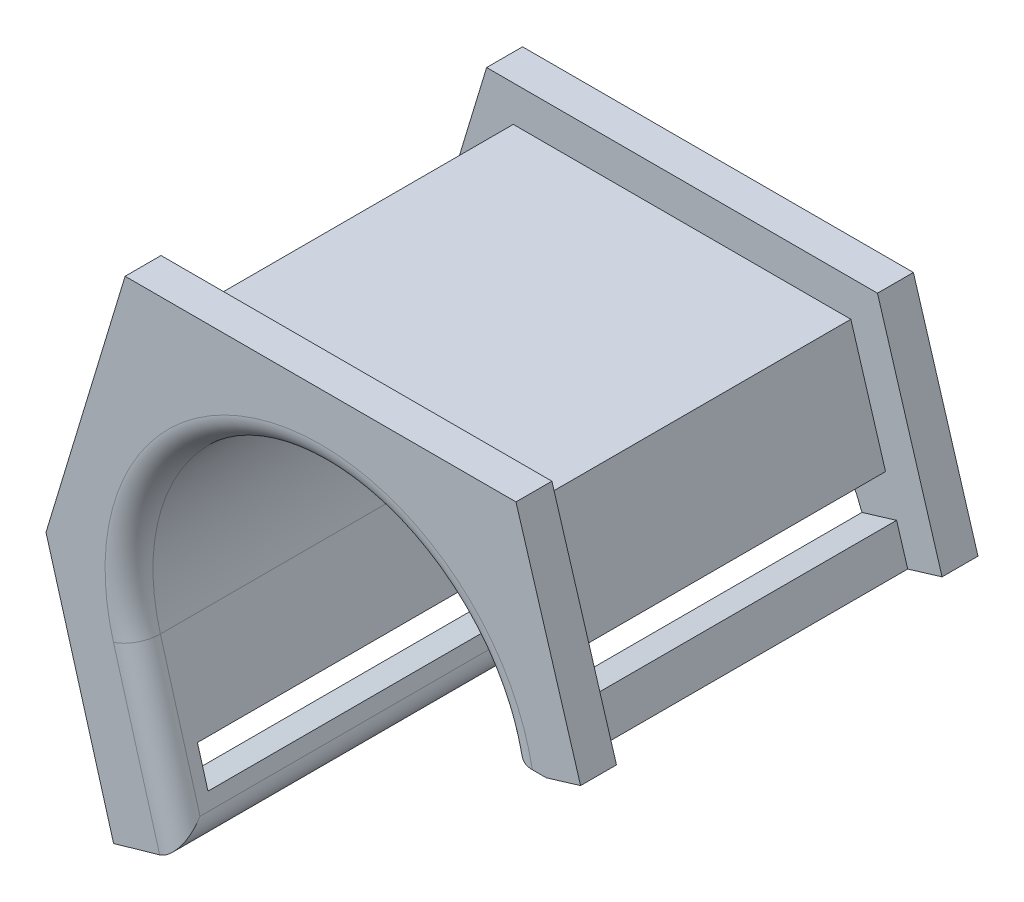
SolidWorks part; units mm, degrees
ref_plane "Front Plane" through (0, 0, 0) normal (0, 0, 1) x (1, 0, 0)
ref_plane "Top Plane" through (0, 0, 0) normal (0, 1, 0) x (1, 0, 0)
ref_plane "Right Plane" through (0, 0, 0) normal (1, 0, 0) x (0, 0, -1)
sketch "Sketch1" plane through (0, 0, 0) normal (0, 0, 1) x (1, 0, 0)
  line L3 (7.05, 9.5) -> (-7.05, 9.5)
  line L8 (9.4257, 1.6517) -> (7.05, 9.5)
  line L10 (-7.05, 9.5) -> (-9.9038, 0.0725)
  line L11 (0, 4) -> (8.7149, 4) construction
  line L12 (-9.9038, 0.0725) -> (-7.202, -9.3478)
  line L13 (0, 0) -> (0, 8) construction
  line L14 (-7.202, -9.3478) -> (-5.7602, -8.9342)
  line L15 (0, 4) -> (-8.7149, 4) construction
  line L16 (9.4257, 1.6517) -> (7.8276, 1.6517)
  line L17 (-5.7602, -8.9342) -> (-7.69, -2.2055)
  line L18 (7.05, 9.5) -> (9.4257, 9.5) construction
  line L19 (9.4257, 1.6517) -> (9.4257, 9.5) construction
  arc A0 (7.8276, 1.6517) -> (-7.69, -2.2055) centre (0, 0) ccw
  arc A4 (9.3553, 1.6517) -> (-1.6939, -9.3478) centre (0, 0) ccw construction
  arc A5 (9.3553, 1.6517) -> (-1.6939, -9.3478) centre (0, 0) ccw construction
  point P6 (9.692, 9.5)
  dimension "D1" = 16
  dimension "D2" = 1.5
  dimension "D3" = 14.1
  dimension "D4" = 8.2
  dimension "D5" = 9.85
  dimension "D6" = 9.8
  dimension "D7" = 16.841
  dimension "D8" = 7.8483
extrude "Boss-Extrude1" add sketch "Sketch1" along normal blind 16.6
ref_plane "Plane1" through (0, 0, 8.3) normal (0, 0, -1) x (-1, 0, 0)
sketch "Sketch2" plane through (0, 0, 0) normal (0, 0, 1) x (1, 0, 0)
  line L0 (-9.9038, 0.0725) -> (-7.202, -9.3478) construction
  line L1 (-7.05, 9.5) -> (-9.9038, 0.0725) construction
  line L2 (7.05, 9.5) -> (-7.05, 9.5) construction
  line L11 (9.4257, 1.6517) -> (7.05, 9.5) construction
  line L12 (-9.9038, 0.0725) -> (-7.202, -9.3478)
  line L13 (-7.05, 9.5) -> (-9.9038, 0.0725)
  line L14 (7.05, 9.5) -> (-7.05, 9.5)
  line L15 (9.4257, 1.6517) -> (7.05, 9.5)
  line L22 (-8.6439, -9.7613) -> (-7.202, -9.3478)
  line L23 (10.8614, 2.0863) -> (9.4257, 1.6517)
  line L26 (-11.4675, 0.0839) -> (-8.6439, -9.7613)
  line L27 (-8.1632, 11) -> (-11.4675, 0.0839)
  line L28 (8.1632, 11) -> (-8.1632, 11)
  line L29 (10.8614, 2.0863) -> (8.1632, 11)
  line L30 (-11.4675, 0.0839) -> (-8.6439, -9.7613)
  line L31 (-8.1632, 11) -> (-11.4675, 0.0839)
  line L32 (8.1632, 11) -> (-8.1632, 11)
  line L33 (10.8614, 2.0863) -> (8.1632, 11)
  dimension "D1" = 1.5
extrude "Boss-Extrude2" add sketch "Sketch2" along normal up to surface (16.6 mm away) up to face at (-1.9127, 1.2411, 16.6)
extrude "Cut-Extrude1" cut sketch "Sketch2<4>" against normal offset from surface 1.5 and the other way offset from surface 1.5 from surface up to face at (-0.8273, 1.6237, 0) other way up to face at (-0.8273, 1.6237, 16.6) starting at plane "Plane1"
sketch "Sketch2<4>" plane through (0, 0, 0) normal (0, 0, 1) x (1, 0, 0) same geometry as "Sketch2"
ref_axis "Axis1" through (0, 0, 16.6) along (0, 0, -1)
ref_plane "Plane2" through (0, 0, 0) normal (1, 0, 0) x (0, 0, -1)
sketch "Sketch3" plane through (9.0925, 2.7524, 0) normal (0.9571, 0.2897, 0) x (0, 0, -1)
  line L0 (-1.5, 8.1632) -> (-1.5, -1.15) construction
  line L1 (-15.1, 2.05) -> (-1.5, 2.05)
  line L2 (-15.1, 2.05) -> (-15.1, 0.45)
  line L3 (-15.1, 0.45) -> (-1.5, 0.45)
  line L4 (-1.5, 2.05) -> (-1.5, 0.45)
  line L5 (-15.1, -1.15) -> (-15.1, 8.1632) construction
  line L6 (-8.3, 0.45) -> (-8.3, -1.15) construction
  line L7 (-1.5, -1.15) -> (-15.1, -1.15) construction
  dimension "D1" = 1.6
extrude "Cut-Extrude2" cut sketch "Sketch3" against normal up to surface (1.7671 mm away) up to face at (-0.9305, 3.7434, 8.3)
sketch "Sketch4" plane through (-9.1318, -2.619, 0) normal (-0.9612, -0.2757, 0) x (0, 0, 1)
  line L0 (15.1, -7) -> (15.1, 2.8) construction
  line L1 (15.1, -3.8) -> (1.5, -3.8)
  line L2 (15.1, -3.8) -> (15.1, -5.4)
  line L3 (15.1, -5.4) -> (1.5, -5.4)
  line L4 (1.5, -3.8) -> (1.5, -5.4)
  line L5 (8.3, -5.4) -> (8.3, -7) construction
  line L6 (1.5, -7) -> (15.1, -7) construction
  line L7 (1.5, 2.8) -> (1.5, -7) construction
  dimension "D1" = 1.6
extrude "Cut-Extrude3" cut sketch "Sketch4" against normal up to surface (1.5 mm away) up to face at (-6.7251, -5.5699, 8.3)
fillet "Fillet1" radius 1 6 edges at (-5.7602, -8.9342, 8.3) (7.8276, 1.6517, 8.3) (-6.7251, -5.5699, 16.6) (-6.7251, -5.5699, 0) (-1.9298, 7.7637, 16.6) (-1.9298, 7.7637, 0)
equation "\"D1@Boss-Extrude1\"=1.36cm+2*1.5mm"
